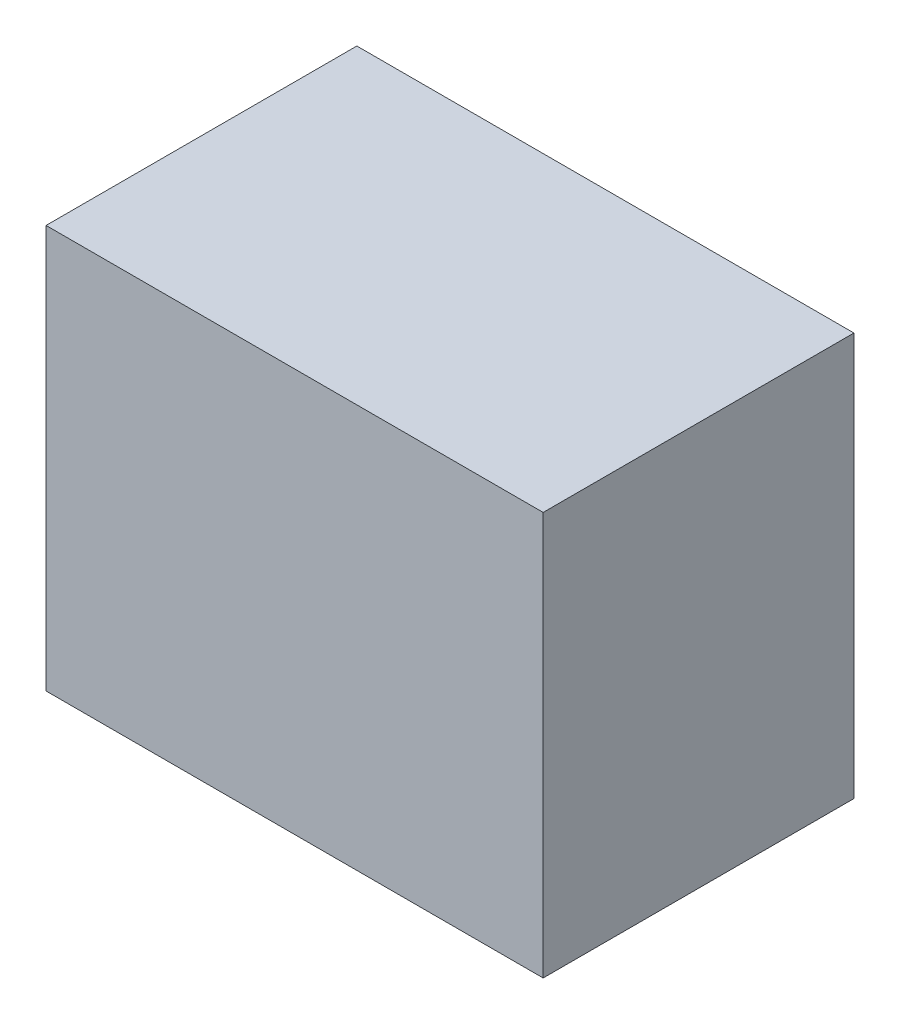
SolidWorks part; units mm, degrees
ref_plane "Front Plane" through (0, 0, 0) normal (0, 0, 1) x (1, 0, 0)
ref_plane "Top Plane" through (0, 0, 0) normal (0, 1, 0) x (1, 0, 0)
ref_plane "Right Plane" through (0, 0, 0) normal (1, 0, 0) x (0, 0, -1)
sketch "Sketch2" plane through (0, 0, 0) normal (0, 0, 1) x (1, 0, 0)
  line L1 (-67.2388, -54.5382) -> (67.2388, -54.5382)
  line L2 (-67.2388, -54.5382) -> (-67.2388, 54.5382)
  line L3 (-67.2388, 54.5382) -> (67.2388, 54.5382)
  line L4 (67.2388, -54.5382) -> (67.2388, 54.5382)
  line L5 (-67.2388, -54.5382) -> (67.2388, 54.5382) construction
  line L6 (-67.2388, 54.5382) -> (67.2388, -54.5382) construction
  point P0 (0, 0)
extrude "Boss-Extrude1" add sketch "Sketch2" along normal blind 84.074
